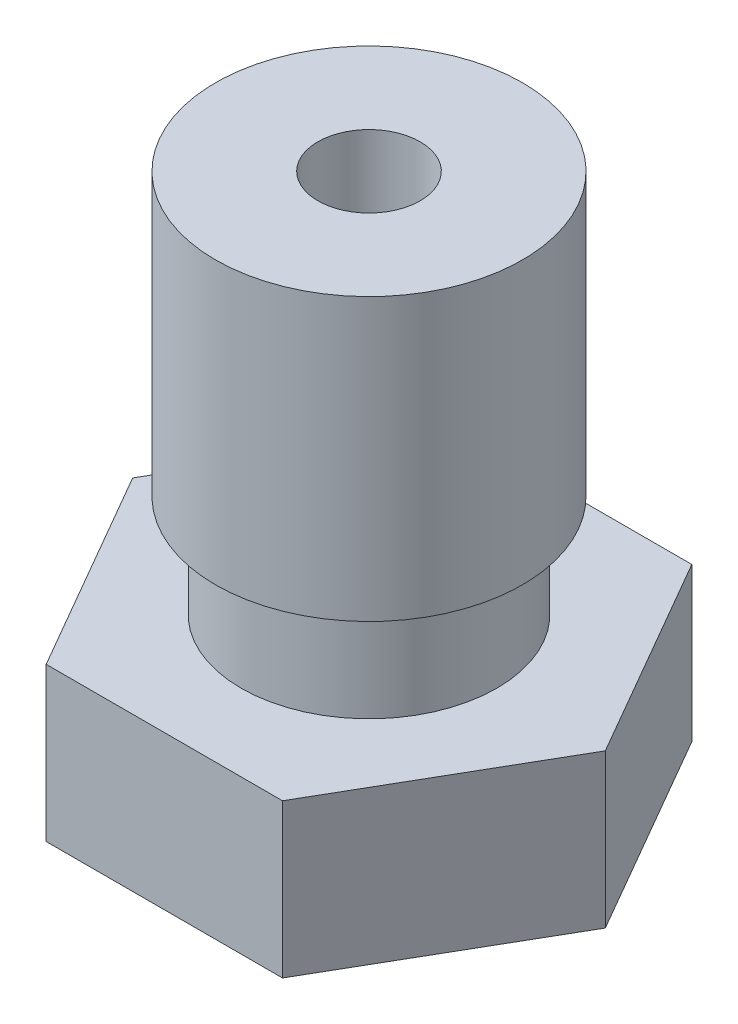
SolidWorks part; units mm, degrees
material "Brass"
ref_plane "Front Plane" through (0, 0, 0) normal (0, 0, 1) x (1, 0, 0)
ref_plane "Top Plane" through (0, 0, 0) normal (0, 1, 0) x (1, 0, 0)
ref_plane "Right Plane" through (0, 0, 0) normal (1, 0, 0) x (0, 0, -1)
sketch "Sketch1" plane through (0, 0, 0) normal (0, 1, 0) x (1, 0, 0)
  line L1 (2.3094, 4) -> (-2.3094, 4)
  line L2 (-2.3094, 4) -> (-4.6188, 0)
  line L3 (-4.6188, 0) -> (-2.3094, -4)
  line L4 (-2.3094, -4) -> (2.3094, -4)
  line L5 (2.3094, -4) -> (4.6188, 0)
  line L6 (4.6188, 0) -> (2.3094, 4)
  circle A0 centre (0, 0) radius 4 construction
  circle A1 centre (0, 0) radius 1
  dimension "D2" = 2
  dimension "D1" = 8
extrude "Boss-Extrude1" add sketch "Sketch1" along normal blind 3
sketch "Sketch2" plane through (0, 0, 0) normal (0, 0, 1) x (1, 0, 0)
  line L0 (1, 0) -> (0.225, -2)
  line L1 (-2.3094, 0) -> (2.3094, 0) construction
  line L2 (0.225, -2) -> (0.6, -2)
  line L3 (0.6, -2) -> (2.0004, 0)
  line L4 (2.3094, 0) -> (4.6188, 0) construction
  line L5 (0, -2) -> (0, 8.8072) construction
  line L6 (1, 0) -> (2.0004, 0)
  line L7 (1, 3) -> (1, 10.5)
  line L8 (-2.3094, 3) -> (2.3094, 3) construction
  line L9 (1, 10.5) -> (3, 10.5)
  line L10 (3, 10.5) -> (3, 5)
  line L11 (3, 5) -> (2.5, 5)
  line L12 (2.5, 5) -> (2.5, 3)
  line L13 (2.3094, 3) -> (4.6188, 3) construction
  line L14 (2.5, 3) -> (1, 3)
  line L15 (1, 3) -> (1.0359, 2.9796)
  dimension "D1" = 0.6
  dimension "D2" = 2
  dimension "D3" = 0.225
  dimension "D4" = 125
  dimension "D6" = 6
  dimension "D7" = 5.5
  dimension "D8" = 0.5
  dimension "D9" = 2
revolve "Revolve1" add sketch "Sketch2" angle 360 about L5 region at (1.0388, -0.8484, 0) region at (1.9464, 6.9464, 0)
